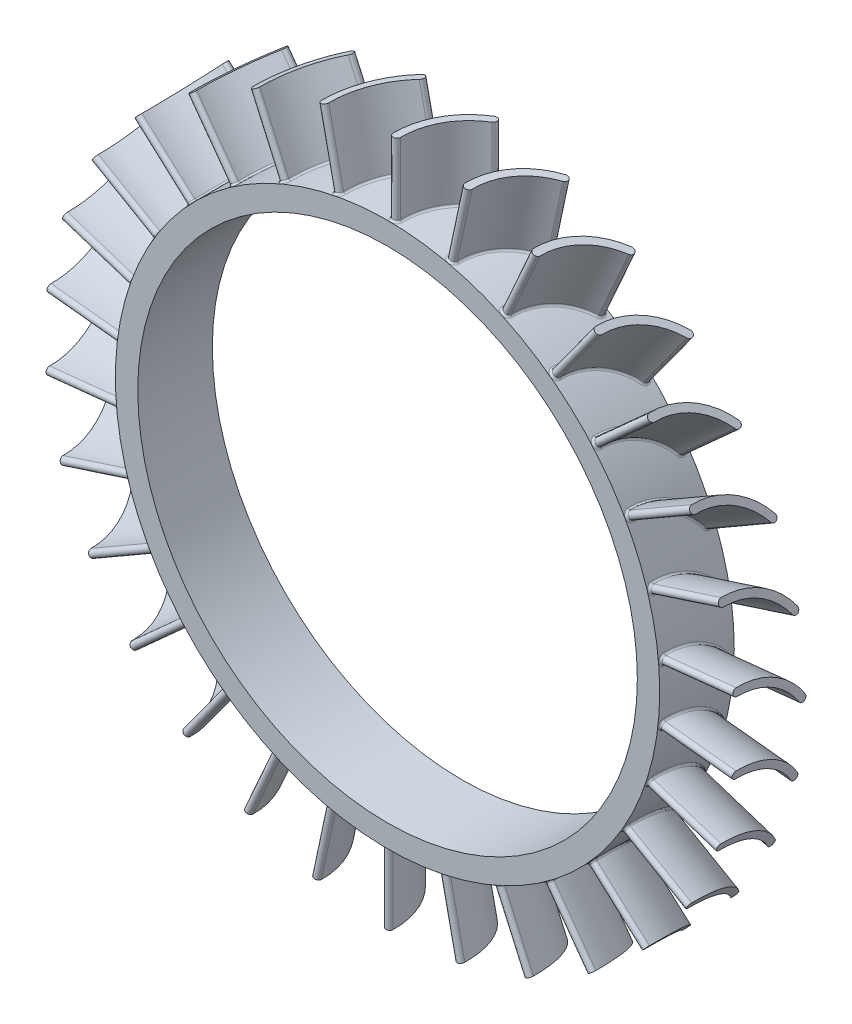
SolidWorks part; units mm, degrees
ref_plane "Front Plane" through (0, 0, 0) normal (0, 0, 1) x (1, 0, 0)
ref_plane "Top Plane" through (0, 0, 0) normal (0, 1, 0) x (1, 0, 0)
ref_plane "Right Plane" through (0, 0, 0) normal (1, 0, 0) x (0, 0, -1)
sketch "Sketch1" plane through (0, 0, 0) normal (0, 0, 1) x (1, 0, 0)
  circle A0 centre (0, 0) radius 73
  circle A1 centre (0, 0) radius 67
  dimension "D1" = 134
  dimension "D2" = 146
extrude "Boss-Extrude1" add sketch "Sketch1" along normal mid plane 20
sketch "Sketch2" plane through (0, 0, 0) normal (0, 1, 0) x (1, 0, 0)
  line L0 (-73, -10) -> (73, -10) construction
  line L1 (67, 10) -> (-67, 10) construction
  arc A0 (-0.0154, -8.5) -> (9.6648, 9) centre (19.9812, -8.1339) cw
  arc A1 (1.9843, -8.4634) -> (10.6964, 7.2866) centre (19.9812, -8.1339) cw
  arc A3 (-0.0154, -8.5) -> (1.9843, -8.4634) centre (0.9844, -8.4817) ccw
  arc A4 (9.6648, 9) -> (10.6964, 7.2866) centre (10.1806, 8.1433) cw
  dimension "D3" = 20
  dimension "D1" = 1.5
  dimension "D2" = 1
  dimension "D4" = 2
extrude "Boss-Extrude2" add sketch "Sketch2" along normal blind 24.5 from offset 68
fillet "Fillet1" radius 0.5 4 edges at (0.8792, 72.9947, 9.4761) (1.2928, 72.9886, 1.0105) (9.2833, 72.4073, -7.7018) (2.4685, 72.9583, 3.9741)
pattern_circular "CirPattern1" count 30 over 360 about axis through (0, 0, 10) along (0, 0, -1) of "Boss-Extrude2", "Fillet1"
